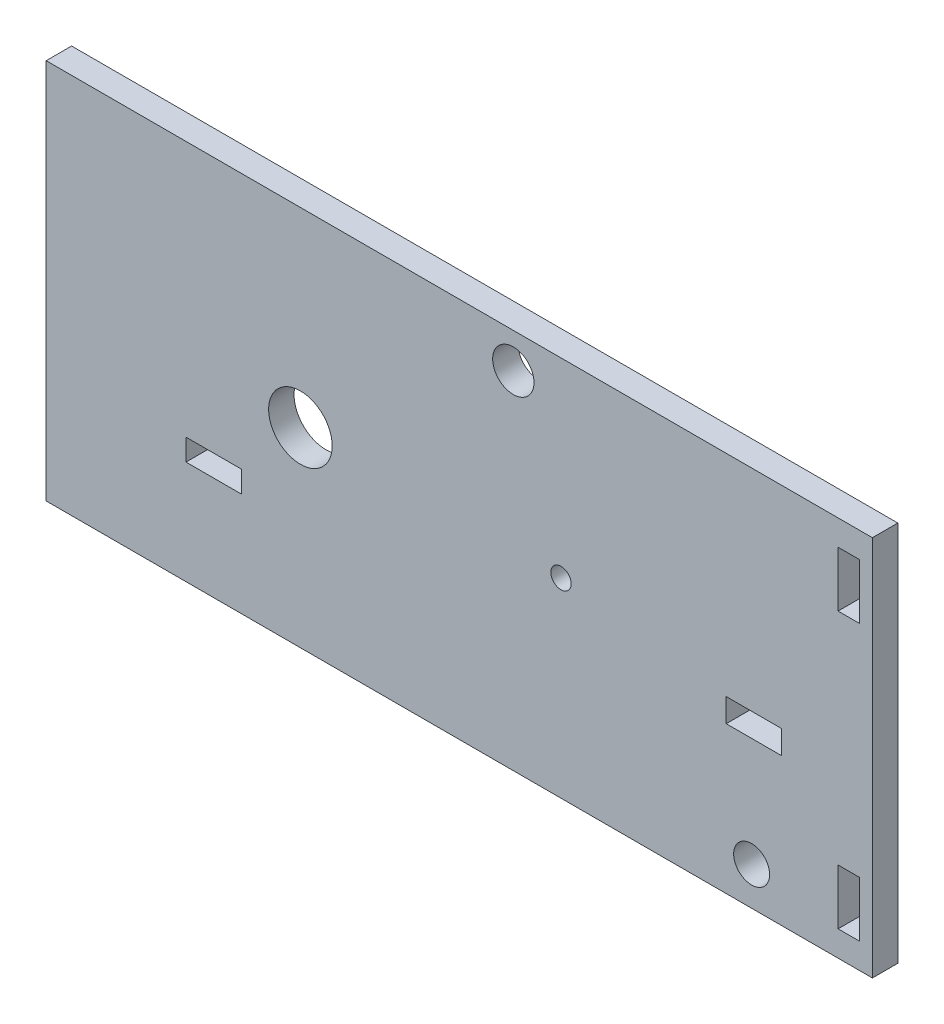
SolidWorks part; units mm, degrees
ref_plane "Front Plane" through (0, 0, 0) normal (0, 0, 1) x (1, 0, 0)
ref_plane "Top Plane" through (0, 0, 0) normal (0, 1, 0) x (1, 0, 0)
ref_plane "Right Plane" through (0, 0, 0) normal (1, 0, 0) x (0, 0, -1)
sketch "Sketch1" plane through (0, 0, 0) normal (0, 0, 1) x (1, 0, 0)
  line L0 (-55.3, -10.3) -> (-55.3, -13.7)
  line L1 (-86, -30) -> (44, -30)
  line L2 (-86, -30) -> (-86, 30)
  line L3 (-86, 30) -> (44, 30)
  line L4 (44, -30) -> (44, 30)
  line L5 (-64, -10.3) -> (-55.3, -10.3)
  line L6 (-64, -10.3) -> (-64, -13.7)
  line L7 (-64, -13.7) -> (-55.3, -13.7)
  line L13 (29.7, -5) -> (21, -5) construction
  line L14 (-55.3, -12) -> (-64, -12) construction
  line L15 (-59.65, -10.3) -> (-59.65, -13.7) construction
  line L16 (40.3, 26) -> (40.3, 17.3) construction
  line L17 (38.6, 26) -> (42, 26)
  line L18 (38.6, 26) -> (38.6, 17.3)
  line L19 (38.6, 17.3) -> (42, 17.3)
  line L20 (42, 26) -> (42, 17.3)
  line L21 (38.6, -17.3) -> (42, -17.3)
  line L22 (38.6, -17.3) -> (38.6, -26)
  line L23 (38.6, -26) -> (42, -26)
  line L24 (42, -17.3) -> (42, -26)
  line L25 (42, 21.65) -> (38.6, 21.65) construction
  line L26 (40.3, -17.3) -> (40.3, -26) construction
  line L27 (42, -21.65) -> (38.6, -21.65) construction
  line L28 (21, -3.15) -> (29.7, -3.15)
  line L29 (21, -3.15) -> (21, -6.85)
  line L30 (21, -6.85) -> (29.7, -6.85)
  line L31 (29.7, -3.15) -> (29.7, -6.85)
  line L32 (25.35, -6.85) -> (25.35, -3.15) construction
  circle A2 centre (-46, 0) radius 5
  circle A3 centre (-12.5, 24.5) radius 3.25
  circle A4 centre (25, -24) radius 2.83
  circle A5 centre (-5, 0) radius 1.6
  point P1 (0, 0)
  point P24 (-86, 0)
  dimension "D10" = 6.5
  dimension "D14" = 5.66
  dimension "D21" = 10
  dimension "D2" = 60
  dimension "D4" = 130
  dimension "D6" = 8.7
  dimension "D8" = 3.4
  dimension "D12" = 111
  dimension "D19" = 24.5
  dimension "D13" = 24
  dimension "D5" = 40
  dimension "D7" = 33.5
  dimension "D9" = 7.5
  dimension "D11" = 26.35
  dimension "D15" = 126.3
  dimension "D17" = 21.65
  dimension "D18" = 21.65
  dimension "D16" = 85
  dimension "D3" = 5
  dimension "D20" = 12
extrude "Boss-Extrude1" add sketch "Sketch1" along normal mid plane 4
sketch "Sketch2" plane through (0, 0, 2) normal (0, 0, 1) x (1, 0, 0)
  line L0 (40.3, 26) -> (40.3, 17.3) construction
  line L1 (42, 21.65) -> (38.6, 21.65) construction
  line L2 (40.3, -17.3) -> (40.3, -26) construction
  line L3 (42, -17.3) -> (38.6, -17.3) construction
  line L4 (38.6, -26) -> (42, -26) construction
  line L5 (38.6, -21.65) -> (42, -21.65) construction
  line L6 (38.6, -17.3) -> (38.6, -26) construction
  line L7 (42, -26) -> (42, -17.3) construction
sketch "Sketch4" plane through (0, 0, -2) normal (0, 0, -1) x (-1, 0, 0)
  line L0 (59.65, -10.3) -> (59.65, -13.7) construction
  line L1 (55.3, -12) -> (64, -12) construction
  line L2 (-29.7, -5) -> (-21, -5) construction
  line L3 (-29.7, -6.85) -> (-29.7, -3.15) construction
  line L4 (-21, -3.15) -> (-21, -6.85) construction
  line L5 (-25.35, -3.15) -> (-25.35, -6.85) construction
  line L6 (-29.7, -3.15) -> (-21, -3.15) construction
  line L7 (-21, -6.85) -> (-29.7, -6.85) construction
equation "\"padding\"=4"
equation "\"hole_width\"=3.4"
equation "\"hole_height\"=8.7"
equation "\"back_boost\"= 7"
equation "\"D5@Sketch1\"=33+\"back_boost\""
equation "\"D12@Sketch1\"=104+\"back_boost\""
equation "\"D15@Sketch1\"=119.30mm+\"back_boost\""
equation "\"D11@Sketch1\"=\"back_boost\"+19.35mm"
equation "\"D4@Sketch1\"=\"back_boost\"+123.00mm"
